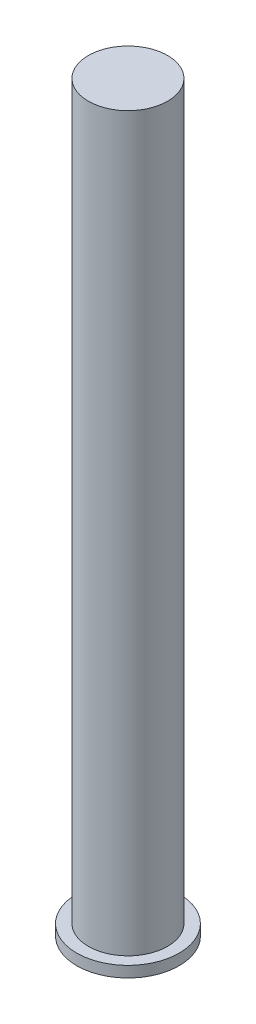
SolidWorks part; units mm, degrees
material "6061-T6 (SS)"
ref_plane "Front Plane" through (0, 0, 0) normal (1, 0, 0) x (0, 1, 0)
ref_plane "Top Plane" through (0, 0, 0) normal (0, 0, 1) x (0, 1, 0)
ref_plane "Right Plane" through (0, 0, 0) normal (0, 1, 0) x (-1, 0, 0)
sketch "Sketch2" plane through (0, 0, 0) normal (1, 0, 0) x (0, 1, 0)
  line L0 (0, 0) -> (-104.14, 0)
  line L1 (-104.14, 0) -> (-104.14, 7.112)
  line L2 (-104.14, 7.112) -> (-101.6, 7.112)
  line L3 (-101.6, 7.112) -> (-101.6, 5.5)
  line L4 (-101.6, 5.5) -> (0, 5.5)
  line L5 (0, 5.5) -> (0, 0)
  arc A0 (-103.124, 7.112) -> (-104.14, 0) centre (-78.74, 0) ccw
  dimension "D1" = 101.6
  dimension "D2" = 2.54
  dimension "D3" = 1.524
  dimension "D4" = 5.5
  dimension "D5" = 7.112
revolve "Revolve1" add sketch "Sketch2" angle 360 about L0 region at (0, -52.2168, 2.7646)
equation "\"D4@Sketch2\"=5.5mm"
